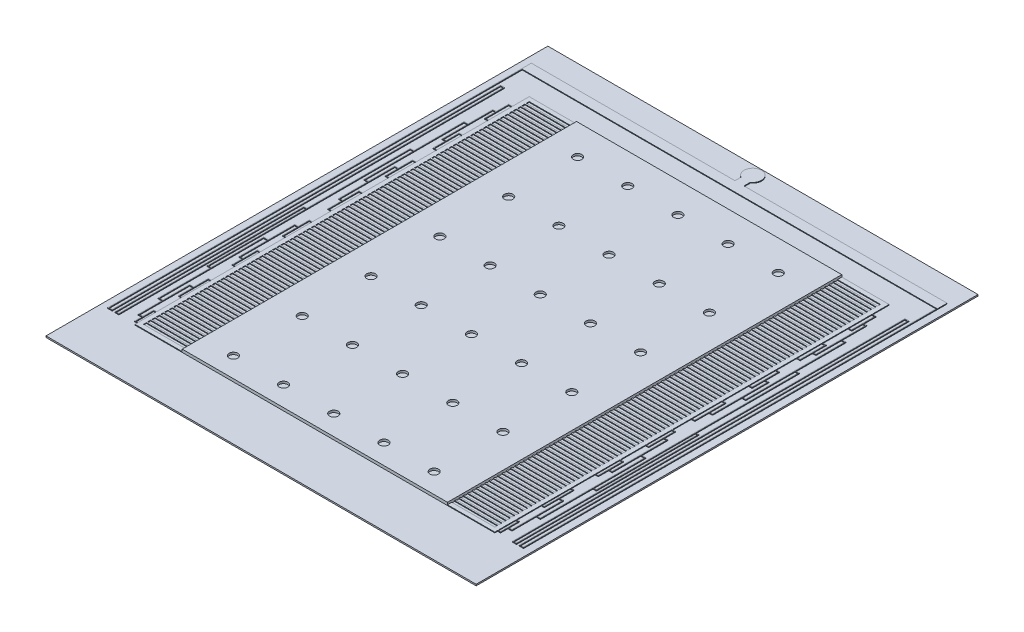
SolidWorks part; units mm, degrees
ref_plane "Front Plane" through (0, 0, 0) normal (0, 0, 1) x (1, 0, 0)
ref_plane "Top Plane" through (0, 0, 0) normal (0, 1, 0) x (1, 0, 0)
ref_plane "Right Plane" through (0, 0, 0) normal (1, 0, 0) x (0, 0, -1)
sketch "Sketch3" plane through (0, 0, 0) normal (0, 1, 0) x (1, 0, 0)
  line L1 (-15, 17.5) -> (15, 17.5)
  line L2 (-15, 17.5) -> (-15, -17.5)
  line L3 (-15, -17.5) -> (15, -17.5)
  line L4 (15, 17.5) -> (15, -17.5)
  line L5 (-15, 17.5) -> (15, -17.5) construction
  line L6 (-15, -17.5) -> (15, 17.5) construction
  point P0 (0, 0)
  dimension "D1" = 30
  dimension "D2" = 35
extrude "Boss-Extrude2" add sketch "Sketch3" along normal blind 0.1
sketch "Sketch4" plane through (0, 0.1, 0) normal (0, 1, 0) x (1, 0, 0)
  line L1 (-9.25, 13.75) -> (9.25, 13.75)
  line L2 (-9.25, 13.75) -> (-9.25, -13.75)
  line L3 (-9.25, -13.75) -> (9.25, -13.75)
  line L4 (9.25, 13.75) -> (9.25, -13.75)
  line L5 (-9.25, 13.75) -> (9.25, -13.75) construction
  line L6 (-9.25, -13.75) -> (9.25, 13.75) construction
  point P0 (0, 0)
  dimension "D1" = 18.5
  dimension "D2" = 27.5
sketch "Sketch6" plane through (0, 0.1, 0) normal (0, 1, 0) x (1, 0, 0)
  line L0 (-14.5, 15.8474) -> (14.5, 15.8474)
  line L1 (14.5, 15.8474) -> (14.5, -13.6942)
  line L2 (-14.5, 15.8474) -> (-14.5, -13.6942)
  line L3 (-9.25, 13.75) -> (-9.25, -13.75)
  line L4 (-9.25, 13.75) -> (-12.55, 13.75)
  line L5 (-9.25, -13.75) -> (-12.55, -13.75)
  line L6 (-12.55, 13.75) -> (-12.55, -13.75)
  line L7 (9.25, 13.75) -> (9.25, -13.75)
  line L8 (9.25, 13.75) -> (12.55, 13.75)
  line L9 (9.25, -13.75) -> (12.55, -13.75)
  line L10 (12.55, 13.75) -> (12.55, -13.75)
  line L11 (-12.55, 12.5818) -> (-12.8114, 12.5818)
  line L12 (-12.55, 12.5318) -> (-12.7614, 12.5318)
  line L13 (-12.55, 10.928) -> (-12.7614, 10.928)
  line L14 (-12.55, 10.878) -> (-12.8114, 10.878)
  line L15 (-12.7614, 12.5318) -> (-12.7614, 10.928)
  line L16 (-12.8114, 12.5818) -> (-12.8114, 11.7021)
  line L17 (-12.8114, 11.7021) -> (-13.0395, 11.7021)
  line L18 (-12.8114, 10.878) -> (-12.8114, 11.6521)
  line L19 (-12.8114, 11.6521) -> (-12.9895, 11.6521)
  line L20 (-12.55, 9.1125) -> (-12.8052, 9.1125)
  line L21 (-12.55, 9.0625) -> (-12.7552, 9.0625)
  line L22 (-12.7552, 9.0625) -> (-12.7552, 7.3412)
  line L23 (-12.7552, 7.3412) -> (-12.55, 7.3412)
  line L24 (-12.55, 7.2912) -> (-12.8052, 7.2912)
  line L25 (-12.8052, 7.2912) -> (-12.8052, 8.1575)
  line L26 (-13.0395, 11.7021) -> (-13.0395, 9.9736)
  line L27 (-12.8052, 9.1125) -> (-12.8052, 8.2075)
  line L28 (-12.8052, 8.2075) -> (-12.9895, 8.2075)
  line L29 (-12.55, 5.8632) -> (-12.7979, 5.8632)
  line L30 (-12.7979, 5.8632) -> (-12.7979, 4.8722)
  line L31 (-12.7979, 4.8722) -> (-13.0441, 4.8722)
  line L32 (-12.55, 3.9456) -> (-12.7979, 3.9456)
  line L33 (-12.7979, 3.9456) -> (-12.7979, 4.8222)
  line L34 (-12.7979, 4.8222) -> (-12.9941, 4.8222)
  line L35 (-12.55, 5.8132) -> (-12.7479, 5.8132)
  line L36 (-12.7479, 5.8132) -> (-12.7479, 3.9956)
  line L37 (-12.7479, 3.9956) -> (-12.55, 3.9956)
  line L38 (-12.55, 2.1314) -> (-12.8017, 2.1314)
  line L39 (-12.8017, 2.1314) -> (-12.8017, 0.9895)
  line L40 (-12.8017, 0.9895) -> (-12.9941, 0.9895)
  line L41 (-12.55, -0.05) -> (-12.8017, -0.05)
  line L42 (-12.8017, -0.05) -> (-12.8017, 0.9395)
  line L43 (-13.0441, 4.8722) -> (-13.0441, 3.0344)
  line L44 (-12.55, 2.0814) -> (-12.7517, 2.0814)
  line L45 (-12.7517, 2.0814) -> (-12.7517, 0)
  line L46 (-12.7517, 0) -> (-12.55, 0)
  line L47 (-12.55, -1.363) -> (-12.7705, -1.363)
  line L48 (-12.7705, -1.363) -> (-12.7705, -2.1377)
  line L49 (-13.0441, 3.0344) -> (-13.2661, 3.0344)
  line L50 (-12.55, -3.2374) -> (-12.7705, -3.2374)
  line L51 (-12.7705, -3.2374) -> (-12.7705, -2.1877)
  line L52 (-12.7705, -2.1877) -> (-12.9647, -2.1877)
  line L53 (-12.55, -1.413) -> (-12.7205, -1.413)
  line L54 (-12.7205, -1.413) -> (-12.7205, -3.1874)
  line L55 (-12.7205, -3.1874) -> (-12.55, -3.1874)
  line L56 (-12.55, -4.9884) -> (-12.7705, -4.9884)
  line L57 (-12.7705, -4.9884) -> (-12.7705, -5.9807)
  line L58 (-12.7705, -5.9807) -> (-12.9647, -5.9807)
  line L59 (-12.55, -6.7484) -> (-12.7705, -6.7484)
  line L60 (-12.7705, -6.7484) -> (-12.7705, -6.0307)
  line L61 (-12.8017, 0.9395) -> (-13.0441, 0.9395)
  line L62 (-12.7205, -5.0384) -> (-12.7205, -6.6984)
  line L63 (-12.7205, -6.6984) -> (-12.55, -6.6984)
  line L64 (-12.7205, -5.0384) -> (-12.55, -5.0384)
  line L65 (-12.55, -8.422) -> (-12.7572, -8.422)
  line L66 (-12.7572, -8.422) -> (-12.7572, -9.4377)
  line L67 (-13.0441, 0.9395) -> (-13.0441, 2.9844)
  line L68 (-12.55, -10.502) -> (-12.7572, -10.502)
  line L69 (-12.7572, -10.502) -> (-12.7572, -9.4877)
  line L70 (-12.7572, -9.4877) -> (-12.9899, -9.4877)
  line L71 (-12.55, -8.472) -> (-12.7072, -8.472)
  line L72 (-12.7072, -8.472) -> (-12.7072, -10.452)
  line L73 (-12.7072, -10.452) -> (-12.55, -10.452)
  line L74 (-12.55, -12.2327) -> (-12.7572, -12.2327)
  line L75 (-12.7572, -12.2327) -> (-12.7572, -12.9898)
  line L76 (-12.7572, -12.9898) -> (-12.9899, -12.9898)
  line L77 (-12.55, -13.5571) -> (-12.7572, -13.5571)
  line L78 (-12.7572, -13.5571) -> (-12.7572, -13.0398)
  line L79 (-13.0395, 9.9736) -> (-13.3161, 9.9736)
  line L80 (-12.7072, -12.2827) -> (-12.7072, -13.5071)
  line L81 (-12.7072, -13.5071) -> (-12.55, -13.5071)
  line L82 (-13.3161, 9.9736) -> (-13.3161, 6.4717)
  line L83 (-12.8052, 8.1575) -> (-13.0395, 8.1575)
  line L84 (-13.0395, 8.1575) -> (-13.0395, 9.9236)
  line L85 (-13.0395, 9.9236) -> (-13.2661, 9.9236)
  line L86 (-12.9895, 11.6521) -> (-12.9895, 8.2075)
  line L87 (-12.9941, 4.8222) -> (-12.9941, 0.9895)
  line L88 (-12.7705, -6.0307) -> (-13.0147, -6.0307)
  line L89 (-13.0147, -6.0307) -> (-13.0147, -4.0382)
  line L90 (-13.0147, -4.0382) -> (-13.2808, -4.0382)
  line L91 (-12.7705, -2.1377) -> (-13.0147, -2.1377)
  line L92 (-13.0147, -2.1377) -> (-13.0147, -3.9882)
  line L93 (-13.0147, -3.9882) -> (-13.3308, -3.9882)
  line L94 (-12.9647, -2.1877) -> (-12.9647, -5.9807)
  line L95 (-12.7572, -9.4377) -> (-13.0399, -9.4377)
  line L96 (-13.0399, -9.4377) -> (-13.0399, -11.3027)
  line L97 (-13.0399, -11.3027) -> (-13.2808, -11.3027)
  line L98 (-12.7572, -13.0398) -> (-13.0399, -13.0398)
  line L99 (-13.0399, -13.0398) -> (-13.0399, -11.3527)
  line L100 (-13.3308, -3.9882) -> (-13.3308, -7.6362)
  line L101 (-12.9899, -9.4877) -> (-12.9899, -12.9898)
  line L102 (-13.3161, 6.4717) -> (-13.5698, 6.4717)
  line L103 (-13.3161, 2.9844) -> (-13.3161, 6.4217)
  line L104 (-13.3161, 6.4217) -> (-13.5198, 6.4217)
  line L105 (-13.2661, 9.9236) -> (-13.2661, 3.0344)
  line L106 (-13.3161, 2.9844) -> (-13.0441, 2.9844)
  line L107 (-13.3308, -7.6362) -> (-13.5198, -7.6362)
  line L108 (-13.0399, -11.3527) -> (-13.3308, -11.3527)
  line L109 (-13.3308, -11.3527) -> (-13.3308, -7.6862)
  line L110 (-13.5698, 6.4717) -> (-13.5698, -0.7493)
  line L111 (-13.2808, -4.0382) -> (-13.2808, -11.3027)
  line L112 (-13.5698, -0.7493) -> (-13.7743, -0.7493)
  line L113 (-13.3308, -7.6862) -> (-13.5698, -7.6862)
  line L114 (-13.5698, -7.6862) -> (-13.5698, -0.7993)
  line L115 (-13.5198, -7.6362) -> (-13.5198, 6.4217)
  line L116 (-12.7072, -12.2827) -> (-12.55, -12.2827)
  line L117 (-14.5, -13.6942) -> (-14.189, -13.6942)
  line L118 (-14.45, 15.1627) -> (14.45, 15.1627)
  line L119 (-14.45, 15.1627) -> (-14.45, -13.6442)
  line L120 (-14.45, -13.6442) -> (-14.239, -13.6442)
  line L121 (-14.239, -13.6442) -> (-14.239, 13.4436)
  line L122 (-14.239, 13.4436) -> (-13.9579, 13.4436)
  line L123 (-13.9579, 13.4436) -> (-13.9579, -13.646)
  line L124 (-13.9579, -13.646) -> (-13.7743, -13.646)
  line L125 (-13.7743, -13.646) -> (-13.7743, -0.7493)
  line L126 (-14.189, -13.6942) -> (-14.189, 13.3936)
  line L127 (-14.189, 13.3936) -> (-14.0079, 13.3936)
  line L128 (-14.0079, 13.3936) -> (-14.0079, -13.696)
  line L129 (-14.0079, -13.696) -> (-13.7243, -13.696)
  line L130 (-13.7243, -13.696) -> (-13.7243, -0.7993)
  line L131 (-13.7243, -0.7993) -> (-13.5698, -0.7993)
  line L132 (0, -18.8163) -> (0, 18.8163) construction
  line L134 (14.45, 15.1627) -> (14.45, -13.6442)
  line L135 (14.0079, -13.696) -> (13.7243, -13.696)
  line L136 (13.9579, -13.646) -> (13.7743, -13.646)
  line L137 (14.5, -13.6942) -> (14.189, -13.6942)
  line L138 (14.45, -13.6442) -> (14.239, -13.6442)
  line L139 (12.7572, -13.5571) -> (12.7572, -13.0398)
  line L140 (12.55, -13.5571) -> (12.7572, -13.5571)
  line L141 (12.7072, -13.5071) -> (12.55, -13.5071)
  line L142 (12.7572, -13.0398) -> (13.0399, -13.0398)
  line L143 (12.7572, -12.9898) -> (12.9899, -12.9898)
  line L144 (12.7072, -12.2827) -> (12.55, -12.2827)
  line L145 (12.7572, -12.2327) -> (12.7572, -12.9898)
  line L146 (12.7072, -12.2827) -> (12.7072, -13.5071)
  line L147 (12.55, -12.2327) -> (12.7572, -12.2327)
  line L148 (13.0399, -13.0398) -> (13.0399, -11.3527)
  line L149 (13.0399, -11.3527) -> (13.3308, -11.3527)
  line L150 (13.0399, -11.3027) -> (13.2808, -11.3027)
  line L151 (12.55, -10.502) -> (12.7572, -10.502)
  line L152 (12.7072, -10.452) -> (12.55, -10.452)
  line L153 (12.7572, -10.502) -> (12.7572, -9.4877)
  line L154 (13.0399, -9.4377) -> (13.0399, -11.3027)
  line L155 (12.9899, -9.4877) -> (12.9899, -12.9898)
  line L156 (12.7572, -9.4877) -> (12.9899, -9.4877)
  line L157 (12.7572, -9.4377) -> (13.0399, -9.4377)
  line L158 (12.7572, -8.422) -> (12.7572, -9.4377)
  line L159 (12.7072, -8.472) -> (12.7072, -10.452)
  line L160 (12.55, -8.472) -> (12.7072, -8.472)
  line L161 (12.55, -8.422) -> (12.7572, -8.422)
  line L162 (13.3308, -11.3527) -> (13.3308, -7.6862)
  line L163 (13.3308, -7.6862) -> (13.5698, -7.6862)
  line L164 (13.3308, -7.6362) -> (13.5198, -7.6362)
  line L165 (12.55, -6.7484) -> (12.7705, -6.7484)
  line L166 (12.7205, -6.6984) -> (12.55, -6.6984)
  line L167 (12.7705, -6.7484) -> (12.7705, -6.0307)
  line L168 (12.7705, -6.0307) -> (13.0147, -6.0307)
  line L169 (12.7705, -5.9807) -> (12.9647, -5.9807)
  line L170 (12.7705, -4.9884) -> (12.7705, -5.9807)
  line L171 (12.7205, -5.0384) -> (12.7205, -6.6984)
  line L172 (12.7205, -5.0384) -> (12.55, -5.0384)
  line L173 (12.55, -4.9884) -> (12.7705, -4.9884)
  line L174 (13.0147, -6.0307) -> (13.0147, -4.0382)
  line L175 (13.3308, -3.9882) -> (13.3308, -7.6362)
  line L176 (13.2808, -4.0382) -> (13.2808, -11.3027)
  line L177 (13.0147, -4.0382) -> (13.2808, -4.0382)
  line L178 (13.0147, -3.9882) -> (13.3308, -3.9882)
  line L179 (12.55, -3.2374) -> (12.7705, -3.2374)
  line L180 (12.7205, -3.1874) -> (12.55, -3.1874)
  line L181 (13.0147, -2.1377) -> (13.0147, -3.9882)
  line L182 (12.9647, -2.1877) -> (12.9647, -5.9807)
  line L183 (12.7705, -3.2374) -> (12.7705, -2.1877)
  line L184 (12.7705, -2.1877) -> (12.9647, -2.1877)
  line L185 (12.7705, -2.1377) -> (13.0147, -2.1377)
  line L186 (12.7205, -1.413) -> (12.7205, -3.1874)
  line L187 (12.7705, -1.363) -> (12.7705, -2.1377)
  line L188 (12.55, -1.413) -> (12.7205, -1.413)
  line L189 (12.55, -1.363) -> (12.7705, -1.363)
  line L190 (13.5698, -7.6862) -> (13.5698, -0.7993)
  line L191 (13.7243, -13.696) -> (13.7243, -0.7993)
  line L192 (13.7743, -13.646) -> (13.7743, -0.7493)
  line L193 (13.7243, -0.7993) -> (13.5698, -0.7993)
  line L194 (13.5698, -0.7493) -> (13.7743, -0.7493)
  line L195 (12.55, -0.05) -> (12.8017, -0.05)
  line L196 (12.7517, 0) -> (12.55, 0)
  line L197 (12.8017, -0.05) -> (12.8017, 0.9395)
  line L198 (12.8017, 0.9395) -> (13.0441, 0.9395)
  line L199 (12.8017, 0.9895) -> (12.9941, 0.9895)
  line L200 (12.7517, 2.0814) -> (12.7517, 0)
  line L201 (12.8017, 2.1314) -> (12.8017, 0.9895)
  line L202 (12.55, 2.0814) -> (12.7517, 2.0814)
  line L203 (12.55, 2.1314) -> (12.8017, 2.1314)
  line L204 (13.0441, 3.0344) -> (13.2661, 3.0344)
  line L205 (13.3161, 2.9844) -> (13.0441, 2.9844)
  line L206 (13.0441, 0.9395) -> (13.0441, 2.9844)
  line L207 (12.55, 3.9456) -> (12.7979, 3.9456)
  line L208 (12.7479, 3.9956) -> (12.55, 3.9956)
  line L209 (13.0441, 4.8722) -> (13.0441, 3.0344)
  line L210 (12.9941, 4.8222) -> (12.9941, 0.9895)
  line L211 (12.7979, 3.9456) -> (12.7979, 4.8222)
  line L212 (12.7979, 4.8222) -> (12.9941, 4.8222)
  line L213 (12.7979, 4.8722) -> (13.0441, 4.8722)
  line L214 (12.7479, 5.8132) -> (12.7479, 3.9956)
  line L215 (12.7979, 5.8632) -> (12.7979, 4.8722)
  line L216 (12.55, 5.8132) -> (12.7479, 5.8132)
  line L217 (12.55, 5.8632) -> (12.7979, 5.8632)
  line L218 (13.3161, 2.9844) -> (13.3161, 6.4217)
  line L219 (13.5698, 6.4717) -> (13.5698, -0.7493)
  line L220 (13.5198, -7.6362) -> (13.5198, 6.4217)
  line L221 (13.3161, 6.4217) -> (13.5198, 6.4217)
  line L222 (13.3161, 6.4717) -> (13.5698, 6.4717)
  line L223 (12.55, 7.2912) -> (12.8052, 7.2912)
  line L224 (12.7552, 7.3412) -> (12.55, 7.3412)
  line L225 (12.8052, 7.2912) -> (12.8052, 8.1575)
  line L226 (12.8052, 8.1575) -> (13.0395, 8.1575)
  line L227 (12.8052, 8.2075) -> (12.9895, 8.2075)
  line L228 (12.7552, 9.0625) -> (12.7552, 7.3412)
  line L229 (12.8052, 9.1125) -> (12.8052, 8.2075)
  line L230 (12.55, 9.0625) -> (12.7552, 9.0625)
  line L231 (12.55, 9.1125) -> (12.8052, 9.1125)
  line L232 (13.0395, 8.1575) -> (13.0395, 9.9236)
  line L233 (13.3161, 9.9736) -> (13.3161, 6.4717)
  line L234 (13.2661, 9.9236) -> (13.2661, 3.0344)
  line L235 (13.0395, 9.9236) -> (13.2661, 9.9236)
  line L236 (13.0395, 9.9736) -> (13.3161, 9.9736)
  line L237 (12.55, 10.878) -> (12.8114, 10.878)
  line L238 (12.55, 10.928) -> (12.7614, 10.928)
  line L239 (13.0395, 11.7021) -> (13.0395, 9.9736)
  line L240 (12.9895, 11.6521) -> (12.9895, 8.2075)
  line L241 (12.8114, 10.878) -> (12.8114, 11.6521)
  line L242 (12.8114, 11.6521) -> (12.9895, 11.6521)
  line L243 (12.8114, 11.7021) -> (13.0395, 11.7021)
  line L244 (13.9579, 13.4436) -> (13.9579, -13.646)
  line L245 (14.0079, 13.3936) -> (14.0079, -13.696)
  line L246 (14.189, -13.6942) -> (14.189, 13.3936)
  line L247 (14.239, -13.6442) -> (14.239, 13.4436)
  line L248 (14.189, 13.3936) -> (14.0079, 13.3936)
  line L249 (14.239, 13.4436) -> (13.9579, 13.4436)
  line L250 (12.7614, 12.5318) -> (12.7614, 10.928)
  line L251 (12.8114, 12.5818) -> (12.8114, 11.7021)
  line L252 (12.55, 12.5318) -> (12.7614, 12.5318)
  line L253 (12.55, 12.5818) -> (12.8114, 12.5818)
  line L254 (-0.2968, 16.2659) -> (-0.2968, 15.8474)
  line L255 (0.336, 16.2899) -> (0.336, 15.8474)
  circle A0 centre (0, 16.7949) radius 0.6065
  point P0 (-12.55, 0)
  point P3 (0, 15.8474)
  point P14 (-12.55, 0)
  point P19 (-12.55, 7.2912)
  point P21 (-12.55, 10.928)
  point P22 (-12.55, 12.4686)
  point P23 (-12.55, 9.0625)
  point P24 (-12.55, 3.9833)
  point P25 (-12.55, 5.8132)
  point P26 (-12.55, 2.0814)
  point P27 (-12.55, -6.7484)
  point P28 (-12.55, -3.2374)
  point P29 (-12.55, -1.413)
  point P30 (-12.55, -5.0384)
  point P31 (-12.55, -10.502)
  point P32 (-12.55, -8.472)
  point P33 (-12.55, -12.1448)
  point P157 (-13.647, -0.7993)
  point P158 (-12.6352, -6.6984)
  point P162 (0, 15.1627)
  point P177 (0, 0)
  dimension "D1" = 3.3
  dimension "D2" = 3.3
  dimension "D3" = 29
  dimension "D4" = 0.05
  dimension "D5" = 0.05
  dimension "D6" = 0.05
  dimension "D7" = 0.05
  dimension "D8" = 0.05
  dimension "D9" = 0.05
  dimension "D10" = 0.05
  dimension "D11" = 0.05
  dimension "D12" = 0.05
  dimension "D13" = 0.05
  dimension "D14" = 0.05
  dimension "D15" = 0.05
  dimension "D16" = 0.05
  dimension "D17" = 0.05
  dimension "D18" = 0.05
  dimension "D19" = 0.05
  dimension "D20" = 0.05
  dimension "D21" = 0.05
  dimension "D22" = 0.05
  dimension "D23" = 0.05
  dimension "D24" = 0.05
  dimension "D25" = 0.05
  dimension "D26" = 0.05
  dimension "D27" = 0.05
  dimension "D28" = 0.05
  dimension "D29" = 0.05
  dimension "D30" = 0.05
  dimension "D31" = 0.05
  dimension "D32" = 0.05
  dimension "D33" = 0.05
  dimension "D34" = 0.05
  dimension "D35" = 0.05
  dimension "D36" = 0.05
  dimension "D37" = 0.05
  dimension "D38" = 0.05
  dimension "D39" = 0.05
  dimension "D40" = 0.05
  dimension "D41" = 0.05
  dimension "D42" = 0.05
  dimension "D43" = 0.05
  dimension "D44" = 0.05
  dimension "D45" = 0.05
  dimension "D46" = 0.05
  dimension "D47" = 0.05
  dimension "D48" = 0.05
  dimension "D49" = 0.05
  dimension "D50" = 0.05
  dimension "D51" = 0.05
  dimension "D52" = 0.05
  dimension "D53" = 0.05
  dimension "D54" = 0.05
  dimension "D55" = 0.05
  dimension "D56" = 0.05
extrude "Boss-Extrude5" add sketch "Sketch4" along normal blind 0.2 separate body
extrude "Boss-Extrude10" add sketch "Sketch6" along normal blind 0.05 contours L132 L118 L134 L138 L247 L249 L244 L136 L192 L194 L219 L222 L233 L236 L239 L243 L251 L253 L10 L252 L250 L238 L237 L241 L242 L240 L227 L229 L231 L230 L228 L224 L223 L225 L226 L232 L235 L234 L204 L209 L213 L215 L217 L216 L214 L208 | L0 L132 A0 L254 | L132 L0 L255 A0 | A0 L132 | L132 A0 | L118 L132 L0 L2 L117 L126 L127 L128 L129 L130 L131 L114 L113 L109 L108 L99 L98 L78 L77 L6 L81 L80 L116 L74 L75 L76 L101 L70 L69 L68 L73 L72 L71 L65 L66 L95 L96 L97 L111 L90 L89 L88 L60 L59 L63 L62 | L10 L8 L7 L9 | L4 L6 L5 L3 | L3 L4 L6 L5 | L7 L8 L10 L9 region at (-7.3984, 0.1, -15.5183) region at (-0.1536, 0.1, -16.0312) region at (0.1754, 0.1, -16.0354) region at (0.168, 0.1, -15.5183) region at (-0.2574, 0.1, -16.7949) region at (0.2574, 0.1, -16.7949) region at (-10.9, 0.1, 0) region at (10.9, 0.1, 0)
sketch "Sketch7" plane through (0, 0.1, 0) normal (0, 1, 0) x (1, 0, 0)
  line L0 (9.25, 13.45) -> (12.25, 13.45)
  line L1 (9.25, 13.45) -> (9.25, 13.25)
  line L2 (12.25, 13.45) -> (12.25, 13.25)
  line L3 (9.25, 13.25) -> (12.25, 13.25)
  line L4 (9.25, -13.75) -> (9.25, 13.75) construction
  line L7 (9.25, 13.15) -> (12.25, 13.15)
  line L8 (9.25, 13.15) -> (9.25, 12.95)
  line L9 (9.25, 12.95) -> (12.25, 12.95)
  line L10 (12.25, 13.15) -> (12.25, 12.95)
  line L11 (9.25, 12.85) -> (12.25, 12.85)
  line L12 (9.25, 12.85) -> (9.25, 12.65)
  line L13 (9.25, 12.65) -> (12.25, 12.65)
  line L14 (12.25, 12.85) -> (12.25, 12.65)
  line L15 (9.25, 12.55) -> (12.25, 12.55)
  line L16 (9.25, 12.55) -> (9.25, 12.35)
  line L17 (9.25, 12.35) -> (12.25, 12.35)
  line L18 (12.25, 12.55) -> (12.25, 12.35)
  line L19 (9.25, 12.25) -> (12.25, 12.25)
  line L20 (9.25, 12.25) -> (9.25, 12.05)
  line L21 (9.25, 12.05) -> (12.25, 12.05)
  line L22 (12.25, 12.25) -> (12.25, 12.05)
  line L23 (9.25, 11.95) -> (12.25, 11.95)
  line L24 (9.25, 11.95) -> (9.25, 11.75)
  line L25 (9.25, 11.75) -> (12.25, 11.75)
  line L26 (12.25, 11.95) -> (12.25, 11.75)
  line L27 (9.25, 11.65) -> (12.25, 11.65)
  line L28 (9.25, 11.65) -> (9.25, 11.45)
  line L29 (9.25, 11.45) -> (12.25, 11.45)
  line L30 (12.25, 11.65) -> (12.25, 11.45)
  line L31 (9.25, 11.35) -> (12.25, 11.35)
  line L32 (9.25, 11.35) -> (9.25, 11.15)
  line L33 (9.25, 11.15) -> (12.25, 11.15)
  line L34 (12.25, 11.35) -> (12.25, 11.15)
  line L35 (9.25, 11.05) -> (12.25, 11.05)
  line L36 (9.25, 11.05) -> (9.25, 10.85)
  line L37 (9.25, 10.85) -> (12.25, 10.85)
  line L38 (12.25, 11.05) -> (12.25, 10.85)
  line L39 (9.25, 10.75) -> (12.25, 10.75)
  line L40 (9.25, 10.75) -> (9.25, 10.55)
  line L41 (9.25, 10.55) -> (12.25, 10.55)
  line L42 (12.25, 10.75) -> (12.25, 10.55)
  line L43 (9.25, 10.45) -> (12.25, 10.45)
  line L44 (9.25, 10.45) -> (9.25, 10.25)
  line L45 (9.25, 10.25) -> (12.25, 10.25)
  line L46 (12.25, 10.45) -> (12.25, 10.25)
  line L47 (9.25, 10.15) -> (12.25, 10.15)
  line L48 (9.25, 10.15) -> (9.25, 9.95)
  line L49 (9.25, 9.95) -> (12.25, 9.95)
  line L50 (12.25, 10.15) -> (12.25, 9.95)
  line L51 (9.25, 9.85) -> (12.25, 9.85)
  line L52 (9.25, 9.85) -> (9.25, 9.65)
  line L53 (9.25, 9.65) -> (12.25, 9.65)
  line L54 (12.25, 9.85) -> (12.25, 9.65)
  line L55 (9.25, 9.55) -> (12.25, 9.55)
  line L56 (9.25, 9.55) -> (9.25, 9.35)
  line L57 (9.25, 9.35) -> (12.25, 9.35)
  line L58 (12.25, 9.55) -> (12.25, 9.35)
  line L59 (9.25, 9.25) -> (12.25, 9.25)
  line L60 (9.25, 9.25) -> (9.25, 9.05)
  line L61 (9.25, 9.05) -> (12.25, 9.05)
  line L62 (12.25, 9.25) -> (12.25, 9.05)
  line L63 (9.25, 8.95) -> (12.25, 8.95)
  line L64 (9.25, 8.95) -> (9.25, 8.75)
  line L65 (9.25, 8.75) -> (12.25, 8.75)
  line L66 (12.25, 8.95) -> (12.25, 8.75)
  line L67 (9.25, 8.65) -> (12.25, 8.65)
  line L68 (9.25, 8.65) -> (9.25, 8.45)
  line L69 (9.25, 8.45) -> (12.25, 8.45)
  line L70 (12.25, 8.65) -> (12.25, 8.45)
  line L71 (9.25, 8.35) -> (12.25, 8.35)
  line L72 (9.25, 8.35) -> (9.25, 8.15)
  line L73 (9.25, 8.15) -> (12.25, 8.15)
  line L74 (12.25, 8.35) -> (12.25, 8.15)
  line L75 (9.25, 8.05) -> (12.25, 8.05)
  line L76 (9.25, 8.05) -> (9.25, 7.85)
  line L77 (9.25, 7.85) -> (12.25, 7.85)
  line L78 (12.25, 8.05) -> (12.25, 7.85)
  line L79 (9.25, 7.75) -> (12.25, 7.75)
  line L80 (9.25, 7.75) -> (9.25, 7.55)
  line L81 (9.25, 7.55) -> (12.25, 7.55)
  line L82 (12.25, 7.75) -> (12.25, 7.55)
  line L83 (9.25, 7.45) -> (12.25, 7.45)
  line L84 (9.25, 7.45) -> (9.25, 7.25)
  line L85 (9.25, 7.25) -> (12.25, 7.25)
  line L86 (12.25, 7.45) -> (12.25, 7.25)
  line L87 (9.25, 7.15) -> (12.25, 7.15)
  line L88 (9.25, 7.15) -> (9.25, 6.95)
  line L89 (9.25, 6.95) -> (12.25, 6.95)
  line L90 (12.25, 7.15) -> (12.25, 6.95)
  line L91 (9.25, 6.85) -> (12.25, 6.85)
  line L92 (9.25, 6.85) -> (9.25, 6.65)
  line L93 (9.25, 6.65) -> (12.25, 6.65)
  line L94 (12.25, 6.85) -> (12.25, 6.65)
  line L95 (9.25, 6.55) -> (12.25, 6.55)
  line L96 (9.25, 6.55) -> (9.25, 6.35)
  line L97 (9.25, 6.35) -> (12.25, 6.35)
  line L98 (12.25, 6.55) -> (12.25, 6.35)
  line L99 (9.25, 6.25) -> (12.25, 6.25)
  line L100 (9.25, 6.25) -> (9.25, 6.05)
  line L101 (9.25, 6.05) -> (12.25, 6.05)
  line L102 (12.25, 6.25) -> (12.25, 6.05)
  line L103 (9.25, 5.95) -> (12.25, 5.95)
  line L104 (9.25, 5.95) -> (9.25, 5.75)
  line L105 (9.25, 5.75) -> (12.25, 5.75)
  line L106 (12.25, 5.95) -> (12.25, 5.75)
  line L107 (9.25, 5.65) -> (12.25, 5.65)
  line L108 (9.25, 5.65) -> (9.25, 5.45)
  line L109 (9.25, 5.45) -> (12.25, 5.45)
  line L110 (12.25, 5.65) -> (12.25, 5.45)
  line L111 (9.25, 5.35) -> (12.25, 5.35)
  line L112 (9.25, 5.35) -> (9.25, 5.15)
  line L113 (9.25, 5.15) -> (12.25, 5.15)
  line L114 (12.25, 5.35) -> (12.25, 5.15)
  line L115 (9.25, 5.05) -> (12.25, 5.05)
  line L116 (9.25, 5.05) -> (9.25, 4.85)
  line L117 (9.25, 4.85) -> (12.25, 4.85)
  line L118 (12.25, 5.05) -> (12.25, 4.85)
  line L119 (9.25, 4.75) -> (12.25, 4.75)
  line L120 (9.25, 4.75) -> (9.25, 4.55)
  line L121 (9.25, 4.55) -> (12.25, 4.55)
  line L122 (12.25, 4.75) -> (12.25, 4.55)
  line L123 (9.25, 4.45) -> (12.25, 4.45)
  line L124 (9.25, 4.45) -> (9.25, 4.25)
  line L125 (9.25, 4.25) -> (12.25, 4.25)
  line L126 (12.25, 4.45) -> (12.25, 4.25)
  line L127 (9.25, 4.15) -> (12.25, 4.15)
  line L128 (9.25, 4.15) -> (9.25, 3.95)
  line L129 (9.25, 3.95) -> (12.25, 3.95)
  line L130 (12.25, 4.15) -> (12.25, 3.95)
  line L131 (9.25, 3.85) -> (12.25, 3.85)
  line L132 (9.25, 3.85) -> (9.25, 3.65)
  line L133 (9.25, 3.65) -> (12.25, 3.65)
  line L134 (12.25, 3.85) -> (12.25, 3.65)
  line L135 (9.25, 3.55) -> (12.25, 3.55)
  line L136 (9.25, 3.55) -> (9.25, 3.35)
  line L137 (9.25, 3.35) -> (12.25, 3.35)
  line L138 (12.25, 3.55) -> (12.25, 3.35)
  line L139 (9.25, 3.25) -> (12.25, 3.25)
  line L140 (9.25, 3.25) -> (9.25, 3.05)
  line L141 (9.25, 3.05) -> (12.25, 3.05)
  line L142 (12.25, 3.25) -> (12.25, 3.05)
  line L143 (9.25, 2.95) -> (12.25, 2.95)
  line L144 (9.25, 2.95) -> (9.25, 2.75)
  line L145 (9.25, 2.75) -> (12.25, 2.75)
  line L146 (12.25, 2.95) -> (12.25, 2.75)
  line L147 (9.25, 2.65) -> (12.25, 2.65)
  line L148 (9.25, 2.65) -> (9.25, 2.45)
  line L149 (9.25, 2.45) -> (12.25, 2.45)
  line L150 (12.25, 2.65) -> (12.25, 2.45)
  line L151 (9.25, 2.35) -> (12.25, 2.35)
  line L152 (9.25, 2.35) -> (9.25, 2.15)
  line L153 (9.25, 2.15) -> (12.25, 2.15)
  line L154 (12.25, 2.35) -> (12.25, 2.15)
  line L155 (9.25, 2.05) -> (12.25, 2.05)
  line L156 (9.25, 2.05) -> (9.25, 1.85)
  line L157 (9.25, 1.85) -> (12.25, 1.85)
  line L158 (12.25, 2.05) -> (12.25, 1.85)
  line L159 (9.25, 1.75) -> (12.25, 1.75)
  line L160 (9.25, 1.75) -> (9.25, 1.55)
  line L161 (9.25, 1.55) -> (12.25, 1.55)
  line L162 (12.25, 1.75) -> (12.25, 1.55)
  line L163 (9.25, 1.45) -> (12.25, 1.45)
  line L164 (9.25, 1.45) -> (9.25, 1.25)
  line L165 (9.25, 1.25) -> (12.25, 1.25)
  line L166 (12.25, 1.45) -> (12.25, 1.25)
  line L167 (9.25, 1.15) -> (12.25, 1.15)
  line L168 (9.25, 1.15) -> (9.25, 0.95)
  line L169 (9.25, 0.95) -> (12.25, 0.95)
  line L170 (12.25, 1.15) -> (12.25, 0.95)
  line L171 (9.25, 0.85) -> (12.25, 0.85)
  line L172 (9.25, 0.85) -> (9.25, 0.65)
  line L173 (9.25, 0.65) -> (12.25, 0.65)
  line L174 (12.25, 0.85) -> (12.25, 0.65)
  line L175 (9.25, 0.55) -> (12.25, 0.55)
  line L176 (9.25, 0.55) -> (9.25, 0.35)
  line L177 (9.25, 0.35) -> (12.25, 0.35)
  line L178 (12.25, 0.55) -> (12.25, 0.35)
  line L179 (9.25, 0.25) -> (12.25, 0.25)
  line L180 (9.25, 0.25) -> (9.25, 0.05)
  line L181 (9.25, 0.05) -> (12.25, 0.05)
  line L182 (12.25, 0.25) -> (12.25, 0.05)
  line L183 (9.25, -0.05) -> (12.25, -0.05)
  line L184 (9.25, -0.05) -> (9.25, -0.25)
  line L185 (9.25, -0.25) -> (12.25, -0.25)
  line L186 (12.25, -0.05) -> (12.25, -0.25)
  line L187 (9.25, -0.35) -> (12.25, -0.35)
  line L188 (9.25, -0.35) -> (9.25, -0.55)
  line L189 (9.25, -0.55) -> (12.25, -0.55)
  line L190 (12.25, -0.35) -> (12.25, -0.55)
  line L191 (9.25, -0.65) -> (12.25, -0.65)
  line L192 (9.25, -0.65) -> (9.25, -0.85)
  line L193 (9.25, -0.85) -> (12.25, -0.85)
  line L194 (12.25, -0.65) -> (12.25, -0.85)
  line L195 (9.25, -0.95) -> (12.25, -0.95)
  line L196 (9.25, -0.95) -> (9.25, -1.15)
  line L197 (9.25, -1.15) -> (12.25, -1.15)
  line L198 (12.25, -0.95) -> (12.25, -1.15)
  line L199 (9.25, -1.25) -> (12.25, -1.25)
  line L200 (9.25, -1.25) -> (9.25, -1.45)
  line L201 (9.25, -1.45) -> (12.25, -1.45)
  line L202 (12.25, -1.25) -> (12.25, -1.45)
  line L203 (9.25, -1.55) -> (12.25, -1.55)
  line L204 (9.25, -1.55) -> (9.25, -1.75)
  line L205 (9.25, -1.75) -> (12.25, -1.75)
  line L206 (12.25, -1.55) -> (12.25, -1.75)
  line L207 (9.25, -1.85) -> (12.25, -1.85)
  line L208 (9.25, -1.85) -> (9.25, -2.05)
  line L209 (9.25, -2.05) -> (12.25, -2.05)
  line L210 (12.25, -1.85) -> (12.25, -2.05)
  line L211 (9.25, -2.15) -> (12.25, -2.15)
  line L212 (9.25, -2.15) -> (9.25, -2.35)
  line L213 (9.25, -2.35) -> (12.25, -2.35)
  line L214 (12.25, -2.15) -> (12.25, -2.35)
  line L215 (9.25, -2.45) -> (12.25, -2.45)
  line L216 (9.25, -2.45) -> (9.25, -2.65)
  line L217 (9.25, -2.65) -> (12.25, -2.65)
  line L218 (12.25, -2.45) -> (12.25, -2.65)
  line L219 (9.25, -2.75) -> (12.25, -2.75)
  line L220 (9.25, -2.75) -> (9.25, -2.95)
  line L221 (9.25, -2.95) -> (12.25, -2.95)
  line L222 (12.25, -2.75) -> (12.25, -2.95)
  line L223 (9.25, -3.05) -> (12.25, -3.05)
  line L224 (9.25, -3.05) -> (9.25, -3.25)
  line L225 (9.25, -3.25) -> (12.25, -3.25)
  line L226 (12.25, -3.05) -> (12.25, -3.25)
  line L227 (9.25, -3.35) -> (12.25, -3.35)
  line L228 (9.25, -3.35) -> (9.25, -3.55)
  line L229 (9.25, -3.55) -> (12.25, -3.55)
  line L230 (12.25, -3.35) -> (12.25, -3.55)
  line L231 (9.25, -3.65) -> (12.25, -3.65)
  line L232 (9.25, -3.65) -> (9.25, -3.85)
  line L233 (9.25, -3.85) -> (12.25, -3.85)
  line L234 (12.25, -3.65) -> (12.25, -3.85)
  line L235 (9.25, -3.95) -> (12.25, -3.95)
  line L236 (9.25, -3.95) -> (9.25, -4.15)
  line L237 (9.25, -4.15) -> (12.25, -4.15)
  line L238 (12.25, -3.95) -> (12.25, -4.15)
  line L239 (9.25, -4.25) -> (12.25, -4.25)
  line L240 (9.25, -4.25) -> (9.25, -4.45)
  line L241 (9.25, -4.45) -> (12.25, -4.45)
  line L242 (12.25, -4.25) -> (12.25, -4.45)
  line L243 (9.25, -4.55) -> (12.25, -4.55)
  line L244 (9.25, -4.55) -> (9.25, -4.75)
  line L245 (9.25, -4.75) -> (12.25, -4.75)
  line L246 (12.25, -4.55) -> (12.25, -4.75)
  line L247 (9.25, -4.85) -> (12.25, -4.85)
  line L248 (9.25, -4.85) -> (9.25, -5.05)
  line L249 (9.25, -5.05) -> (12.25, -5.05)
  line L250 (12.25, -4.85) -> (12.25, -5.05)
  line L251 (9.25, -5.15) -> (12.25, -5.15)
  line L252 (9.25, -5.15) -> (9.25, -5.35)
  line L253 (9.25, -5.35) -> (12.25, -5.35)
  line L254 (12.25, -5.15) -> (12.25, -5.35)
  line L255 (9.25, -5.45) -> (12.25, -5.45)
  line L256 (9.25, -5.45) -> (9.25, -5.65)
  line L257 (9.25, -5.65) -> (12.25, -5.65)
  line L258 (12.25, -5.45) -> (12.25, -5.65)
  line L259 (9.25, -5.75) -> (12.25, -5.75)
  line L260 (9.25, -5.75) -> (9.25, -5.95)
  line L261 (9.25, -5.95) -> (12.25, -5.95)
  line L262 (12.25, -5.75) -> (12.25, -5.95)
  line L263 (9.25, -6.05) -> (12.25, -6.05)
  line L264 (9.25, -6.05) -> (9.25, -6.25)
  line L265 (9.25, -6.25) -> (12.25, -6.25)
  line L266 (12.25, -6.05) -> (12.25, -6.25)
  line L267 (9.25, -6.35) -> (12.25, -6.35)
  line L268 (9.25, -6.35) -> (9.25, -6.55)
  line L269 (9.25, -6.55) -> (12.25, -6.55)
  line L270 (12.25, -6.35) -> (12.25, -6.55)
  line L271 (9.25, -6.65) -> (12.25, -6.65)
  line L272 (9.25, -6.65) -> (9.25, -6.85)
  line L273 (9.25, -6.85) -> (12.25, -6.85)
  line L274 (12.25, -6.65) -> (12.25, -6.85)
  line L275 (9.25, -6.95) -> (12.25, -6.95)
  line L276 (9.25, -6.95) -> (9.25, -7.15)
  line L277 (9.25, -7.15) -> (12.25, -7.15)
  line L278 (12.25, -6.95) -> (12.25, -7.15)
  line L279 (9.25, -7.25) -> (12.25, -7.25)
  line L280 (9.25, -7.25) -> (9.25, -7.45)
  line L281 (9.25, -7.45) -> (12.25, -7.45)
  line L282 (12.25, -7.25) -> (12.25, -7.45)
  line L283 (9.25, -7.55) -> (12.25, -7.55)
  line L284 (9.25, -7.55) -> (9.25, -7.75)
  line L285 (9.25, -7.75) -> (12.25, -7.75)
  line L286 (12.25, -7.55) -> (12.25, -7.75)
  line L287 (9.25, -7.85) -> (12.25, -7.85)
  line L288 (9.25, -7.85) -> (9.25, -8.05)
  line L289 (9.25, -8.05) -> (12.25, -8.05)
  line L290 (12.25, -7.85) -> (12.25, -8.05)
  line L291 (9.25, -8.15) -> (12.25, -8.15)
  line L292 (9.25, -8.15) -> (9.25, -8.35)
  line L293 (9.25, -8.35) -> (12.25, -8.35)
  line L294 (12.25, -8.15) -> (12.25, -8.35)
  line L295 (9.25, -8.45) -> (12.25, -8.45)
  line L296 (9.25, -8.45) -> (9.25, -8.65)
  line L297 (9.25, -8.65) -> (12.25, -8.65)
  line L298 (12.25, -8.45) -> (12.25, -8.65)
  line L299 (9.25, -8.75) -> (12.25, -8.75)
  line L300 (9.25, -8.75) -> (9.25, -8.95)
  line L301 (9.25, -8.95) -> (12.25, -8.95)
  line L302 (12.25, -8.75) -> (12.25, -8.95)
  line L303 (9.25, -9.05) -> (12.25, -9.05)
  line L304 (9.25, -9.05) -> (9.25, -9.25)
  line L305 (9.25, -9.25) -> (12.25, -9.25)
  line L306 (12.25, -9.05) -> (12.25, -9.25)
  line L307 (9.25, -9.35) -> (12.25, -9.35)
  line L308 (9.25, -9.35) -> (9.25, -9.55)
  line L309 (9.25, -9.55) -> (12.25, -9.55)
  line L310 (12.25, -9.35) -> (12.25, -9.55)
  line L311 (9.25, -9.65) -> (12.25, -9.65)
  line L312 (9.25, -9.65) -> (9.25, -9.85)
  line L313 (9.25, -9.85) -> (12.25, -9.85)
  line L314 (12.25, -9.65) -> (12.25, -9.85)
  line L315 (9.25, -9.95) -> (12.25, -9.95)
  line L316 (9.25, -9.95) -> (9.25, -10.15)
  line L317 (9.25, -10.15) -> (12.25, -10.15)
  line L318 (12.25, -9.95) -> (12.25, -10.15)
  line L319 (9.25, -10.25) -> (12.25, -10.25)
  line L320 (9.25, -10.25) -> (9.25, -10.45)
  line L321 (9.25, -10.45) -> (12.25, -10.45)
  line L322 (12.25, -10.25) -> (12.25, -10.45)
  line L323 (9.25, -10.55) -> (12.25, -10.55)
  line L324 (9.25, -10.55) -> (9.25, -10.75)
  line L325 (9.25, -10.75) -> (12.25, -10.75)
  line L326 (12.25, -10.55) -> (12.25, -10.75)
  line L327 (9.25, -10.85) -> (12.25, -10.85)
  line L328 (9.25, -10.85) -> (9.25, -11.05)
  line L329 (9.25, -11.05) -> (12.25, -11.05)
  line L330 (12.25, -10.85) -> (12.25, -11.05)
  line L331 (9.25, -11.15) -> (12.25, -11.15)
  line L332 (9.25, -11.15) -> (9.25, -11.35)
  line L333 (9.25, -11.35) -> (12.25, -11.35)
  line L334 (12.25, -11.15) -> (12.25, -11.35)
  line L335 (9.25, -11.45) -> (12.25, -11.45)
  line L336 (9.25, -11.45) -> (9.25, -11.65)
  line L337 (9.25, -11.65) -> (12.25, -11.65)
  line L338 (12.25, -11.45) -> (12.25, -11.65)
  line L339 (9.25, -11.75) -> (12.25, -11.75)
  line L340 (9.25, -11.75) -> (9.25, -11.95)
  line L341 (9.25, -11.95) -> (12.25, -11.95)
  line L342 (12.25, -11.75) -> (12.25, -11.95)
  line L343 (9.25, -12.05) -> (12.25, -12.05)
  line L344 (9.25, -12.05) -> (9.25, -12.25)
  line L345 (9.25, -12.25) -> (12.25, -12.25)
  line L346 (12.25, -12.05) -> (12.25, -12.25)
  line L347 (9.25, -12.35) -> (12.25, -12.35)
  line L348 (9.25, -12.35) -> (9.25, -12.55)
  line L349 (9.25, -12.55) -> (12.25, -12.55)
  line L350 (12.25, -12.35) -> (12.25, -12.55)
  line L351 (9.25, -12.65) -> (12.25, -12.65)
  line L352 (9.25, -12.65) -> (9.25, -12.85)
  line L353 (9.25, -12.85) -> (12.25, -12.85)
  line L354 (12.25, -12.65) -> (12.25, -12.85)
  line L355 (9.25, -12.95) -> (12.25, -12.95)
  line L356 (9.25, -12.95) -> (9.25, -13.15)
  line L357 (9.25, -13.15) -> (12.25, -13.15)
  line L358 (12.25, -12.95) -> (12.25, -13.15)
  line L359 (9.25, -13.25) -> (12.25, -13.25)
  line L360 (9.25, -13.25) -> (9.25, -13.45)
  line L361 (9.25, -13.45) -> (12.25, -13.45)
  line L362 (12.25, -13.25) -> (12.25, -13.45)
  line L363 (-9.25, 13.45) -> (-9.25, 13.25)
  line L364 (-9.25, 13.45) -> (-12.25, 13.45)
  line L365 (-9.25, 13.25) -> (-12.25, 13.25)
  line L366 (-12.25, 13.45) -> (-12.25, 13.25)
  line L367 (-9.25, 13.75) -> (-9.25, -13.75) construction
  line L368 (-9.25, 13.15) -> (-9.25, 12.95)
  line L369 (-9.25, 13.15) -> (-12.25, 13.15)
  line L370 (-12.25, 13.15) -> (-12.25, 12.95)
  line L371 (-9.25, 12.95) -> (-12.25, 12.95)
  line L372 (-9.25, 12.85) -> (-9.25, 12.65)
  line L373 (-9.25, 12.85) -> (-12.25, 12.85)
  line L374 (-12.25, 12.85) -> (-12.25, 12.65)
  line L375 (-9.25, 12.65) -> (-12.25, 12.65)
  line L376 (-9.25, 12.55) -> (-9.25, 12.35)
  line L377 (-9.25, 12.55) -> (-12.25, 12.55)
  line L378 (-12.25, 12.55) -> (-12.25, 12.35)
  line L379 (-9.25, 12.35) -> (-12.25, 12.35)
  line L380 (-9.25, 12.25) -> (-9.25, 12.05)
  line L381 (-9.25, 12.25) -> (-12.25, 12.25)
  line L382 (-12.25, 12.25) -> (-12.25, 12.05)
  line L383 (-9.25, 12.05) -> (-12.25, 12.05)
  line L384 (-9.25, 11.95) -> (-9.25, 11.75)
  line L385 (-9.25, 11.95) -> (-12.25, 11.95)
  line L386 (-12.25, 11.95) -> (-12.25, 11.75)
  line L387 (-9.25, 11.75) -> (-12.25, 11.75)
  line L388 (-9.25, 11.65) -> (-9.25, 11.45)
  line L389 (-9.25, 11.65) -> (-12.25, 11.65)
  line L390 (-12.25, 11.65) -> (-12.25, 11.45)
  line L391 (-9.25, 11.45) -> (-12.25, 11.45)
  line L392 (-9.25, 11.35) -> (-9.25, 11.15)
  line L393 (-9.25, 11.35) -> (-12.25, 11.35)
  line L394 (-12.25, 11.35) -> (-12.25, 11.15)
  line L395 (-9.25, 11.15) -> (-12.25, 11.15)
  line L396 (-9.25, 11.05) -> (-9.25, 10.85)
  line L397 (-9.25, 11.05) -> (-12.25, 11.05)
  line L398 (-12.25, 11.05) -> (-12.25, 10.85)
  line L399 (-9.25, 10.85) -> (-12.25, 10.85)
  line L400 (-9.25, 10.75) -> (-9.25, 10.55)
  line L401 (-9.25, 10.75) -> (-12.25, 10.75)
  line L402 (-12.25, 10.75) -> (-12.25, 10.55)
  line L403 (-9.25, 10.55) -> (-12.25, 10.55)
  line L404 (-9.25, 10.45) -> (-9.25, 10.25)
  line L405 (-9.25, 10.45) -> (-12.25, 10.45)
  line L406 (-12.25, 10.45) -> (-12.25, 10.25)
  line L407 (-9.25, 10.25) -> (-12.25, 10.25)
  line L408 (-9.25, 10.15) -> (-9.25, 9.95)
  line L409 (-9.25, 10.15) -> (-12.25, 10.15)
  line L410 (-12.25, 10.15) -> (-12.25, 9.95)
  line L411 (-9.25, 9.95) -> (-12.25, 9.95)
  line L412 (-9.25, 9.85) -> (-9.25, 9.65)
  line L413 (-9.25, 9.85) -> (-12.25, 9.85)
  line L414 (-12.25, 9.85) -> (-12.25, 9.65)
  line L415 (-9.25, 9.65) -> (-12.25, 9.65)
  line L416 (-9.25, 9.55) -> (-9.25, 9.35)
  line L417 (-9.25, 9.55) -> (-12.25, 9.55)
  line L418 (-12.25, 9.55) -> (-12.25, 9.35)
  line L419 (-9.25, 9.35) -> (-12.25, 9.35)
  line L420 (-9.25, 9.25) -> (-9.25, 9.05)
  line L421 (-9.25, 9.25) -> (-12.25, 9.25)
  line L422 (-12.25, 9.25) -> (-12.25, 9.05)
  line L423 (-9.25, 9.05) -> (-12.25, 9.05)
  line L424 (-9.25, 8.95) -> (-9.25, 8.75)
  line L425 (-9.25, 8.95) -> (-12.25, 8.95)
  line L426 (-12.25, 8.95) -> (-12.25, 8.75)
  line L427 (-9.25, 8.75) -> (-12.25, 8.75)
  line L428 (-9.25, 8.65) -> (-9.25, 8.45)
  line L429 (-9.25, 8.65) -> (-12.25, 8.65)
  line L430 (-12.25, 8.65) -> (-12.25, 8.45)
  line L431 (-9.25, 8.45) -> (-12.25, 8.45)
  line L432 (-9.25, 8.35) -> (-9.25, 8.15)
  line L433 (-9.25, 8.35) -> (-12.25, 8.35)
  line L434 (-12.25, 8.35) -> (-12.25, 8.15)
  line L435 (-9.25, 8.15) -> (-12.25, 8.15)
  line L436 (-9.25, 8.05) -> (-9.25, 7.85)
  line L437 (-9.25, 8.05) -> (-12.25, 8.05)
  line L438 (-12.25, 8.05) -> (-12.25, 7.85)
  line L439 (-9.25, 7.85) -> (-12.25, 7.85)
  line L440 (-9.25, 7.75) -> (-9.25, 7.55)
  line L441 (-9.25, 7.75) -> (-12.25, 7.75)
  line L442 (-12.25, 7.75) -> (-12.25, 7.55)
  line L443 (-9.25, 7.55) -> (-12.25, 7.55)
  line L444 (-9.25, 7.45) -> (-9.25, 7.25)
  line L445 (-9.25, 7.45) -> (-12.25, 7.45)
  line L446 (-12.25, 7.45) -> (-12.25, 7.25)
  line L447 (-9.25, 7.25) -> (-12.25, 7.25)
  line L448 (-9.25, 7.15) -> (-9.25, 6.95)
  line L449 (-9.25, 7.15) -> (-12.25, 7.15)
  line L450 (-12.25, 7.15) -> (-12.25, 6.95)
  line L451 (-9.25, 6.95) -> (-12.25, 6.95)
  line L452 (-9.25, 6.85) -> (-9.25, 6.65)
  line L453 (-9.25, 6.85) -> (-12.25, 6.85)
  line L454 (-12.25, 6.85) -> (-12.25, 6.65)
  line L455 (-9.25, 6.65) -> (-12.25, 6.65)
  line L456 (-9.25, 6.55) -> (-9.25, 6.35)
  line L457 (-9.25, 6.55) -> (-12.25, 6.55)
  line L458 (-12.25, 6.55) -> (-12.25, 6.35)
  line L459 (-9.25, 6.35) -> (-12.25, 6.35)
  line L460 (-9.25, 6.25) -> (-9.25, 6.05)
  line L461 (-9.25, 6.25) -> (-12.25, 6.25)
  line L462 (-12.25, 6.25) -> (-12.25, 6.05)
  line L463 (-9.25, 6.05) -> (-12.25, 6.05)
  line L464 (-9.25, 5.95) -> (-9.25, 5.75)
  line L465 (-9.25, 5.95) -> (-12.25, 5.95)
  line L466 (-12.25, 5.95) -> (-12.25, 5.75)
  line L467 (-9.25, 5.75) -> (-12.25, 5.75)
  line L468 (-9.25, 5.65) -> (-9.25, 5.45)
  line L469 (-9.25, 5.65) -> (-12.25, 5.65)
  line L470 (-12.25, 5.65) -> (-12.25, 5.45)
  line L471 (-9.25, 5.45) -> (-12.25, 5.45)
  line L472 (-9.25, 5.35) -> (-9.25, 5.15)
  line L473 (-9.25, 5.35) -> (-12.25, 5.35)
  line L474 (-12.25, 5.35) -> (-12.25, 5.15)
  line L475 (-9.25, 5.15) -> (-12.25, 5.15)
  line L476 (-9.25, 5.05) -> (-9.25, 4.85)
  line L477 (-9.25, 5.05) -> (-12.25, 5.05)
  line L478 (-12.25, 5.05) -> (-12.25, 4.85)
  line L479 (-9.25, 4.85) -> (-12.25, 4.85)
  line L480 (-9.25, 4.75) -> (-9.25, 4.55)
  line L481 (-9.25, 4.75) -> (-12.25, 4.75)
  line L482 (-12.25, 4.75) -> (-12.25, 4.55)
  line L483 (-9.25, 4.55) -> (-12.25, 4.55)
  line L484 (-9.25, 4.45) -> (-9.25, 4.25)
  line L485 (-9.25, 4.45) -> (-12.25, 4.45)
  line L486 (-12.25, 4.45) -> (-12.25, 4.25)
  line L487 (-9.25, 4.25) -> (-12.25, 4.25)
  line L488 (-9.25, 4.15) -> (-9.25, 3.95)
  line L489 (-9.25, 4.15) -> (-12.25, 4.15)
  line L490 (-12.25, 4.15) -> (-12.25, 3.95)
  line L491 (-9.25, 3.95) -> (-12.25, 3.95)
  line L492 (-9.25, 3.85) -> (-9.25, 3.65)
  line L493 (-9.25, 3.85) -> (-12.25, 3.85)
  line L494 (-12.25, 3.85) -> (-12.25, 3.65)
  line L495 (-9.25, 3.65) -> (-12.25, 3.65)
  line L496 (-9.25, 3.55) -> (-9.25, 3.35)
  line L497 (-9.25, 3.55) -> (-12.25, 3.55)
  line L498 (-12.25, 3.55) -> (-12.25, 3.35)
  line L499 (-9.25, 3.35) -> (-12.25, 3.35)
  line L500 (-9.25, 3.25) -> (-9.25, 3.05)
  line L501 (-9.25, 3.25) -> (-12.25, 3.25)
  line L502 (-12.25, 3.25) -> (-12.25, 3.05)
  line L503 (-9.25, 3.05) -> (-12.25, 3.05)
  line L504 (-9.25, 2.95) -> (-9.25, 2.75)
  line L505 (-9.25, 2.95) -> (-12.25, 2.95)
  line L506 (-12.25, 2.95) -> (-12.25, 2.75)
  line L507 (-9.25, 2.75) -> (-12.25, 2.75)
  line L508 (-9.25, 2.65) -> (-9.25, 2.45)
  line L509 (-9.25, 2.65) -> (-12.25, 2.65)
  line L510 (-12.25, 2.65) -> (-12.25, 2.45)
  line L511 (-9.25, 2.45) -> (-12.25, 2.45)
  line L512 (-9.25, 2.35) -> (-9.25, 2.15)
  line L513 (-9.25, 2.35) -> (-12.25, 2.35)
  line L514 (-12.25, 2.35) -> (-12.25, 2.15)
  line L515 (-9.25, 2.15) -> (-12.25, 2.15)
  line L516 (-9.25, 2.05) -> (-9.25, 1.85)
  line L517 (-9.25, 2.05) -> (-12.25, 2.05)
  line L518 (-12.25, 2.05) -> (-12.25, 1.85)
  line L519 (-9.25, 1.85) -> (-12.25, 1.85)
  line L520 (-9.25, 1.75) -> (-9.25, 1.55)
  line L521 (-9.25, 1.75) -> (-12.25, 1.75)
  line L522 (-12.25, 1.75) -> (-12.25, 1.55)
  line L523 (-9.25, 1.55) -> (-12.25, 1.55)
  line L524 (-9.25, 1.45) -> (-9.25, 1.25)
  line L525 (-9.25, 1.45) -> (-12.25, 1.45)
  line L526 (-12.25, 1.45) -> (-12.25, 1.25)
  line L527 (-9.25, 1.25) -> (-12.25, 1.25)
  line L528 (-9.25, 1.15) -> (-9.25, 0.95)
  line L529 (-9.25, 1.15) -> (-12.25, 1.15)
  line L530 (-12.25, 1.15) -> (-12.25, 0.95)
  line L531 (-9.25, 0.95) -> (-12.25, 0.95)
  line L532 (-9.25, 0.85) -> (-9.25, 0.65)
  line L533 (-9.25, 0.85) -> (-12.25, 0.85)
  line L534 (-12.25, 0.85) -> (-12.25, 0.65)
  line L535 (-9.25, 0.65) -> (-12.25, 0.65)
  line L536 (-9.25, 0.55) -> (-9.25, 0.35)
  line L537 (-9.25, 0.55) -> (-12.25, 0.55)
  line L538 (-12.25, 0.55) -> (-12.25, 0.35)
  line L539 (-9.25, 0.35) -> (-12.25, 0.35)
  line L540 (-9.25, 0.25) -> (-9.25, 0.05)
  line L541 (-9.25, 0.25) -> (-12.25, 0.25)
  line L542 (-12.25, 0.25) -> (-12.25, 0.05)
  line L543 (-9.25, 0.05) -> (-12.25, 0.05)
  line L544 (-9.25, -0.05) -> (-9.25, -0.25)
  line L545 (-9.25, -0.05) -> (-12.25, -0.05)
  line L546 (-12.25, -0.05) -> (-12.25, -0.25)
  line L547 (-9.25, -0.25) -> (-12.25, -0.25)
  line L548 (-9.25, -0.35) -> (-9.25, -0.55)
  line L549 (-9.25, -0.35) -> (-12.25, -0.35)
  line L550 (-12.25, -0.35) -> (-12.25, -0.55)
  line L551 (-9.25, -0.55) -> (-12.25, -0.55)
  line L552 (-9.25, -0.65) -> (-9.25, -0.85)
  line L553 (-9.25, -0.65) -> (-12.25, -0.65)
  line L554 (-12.25, -0.65) -> (-12.25, -0.85)
  line L555 (-9.25, -0.85) -> (-12.25, -0.85)
  line L556 (-9.25, -0.95) -> (-9.25, -1.15)
  line L557 (-9.25, -0.95) -> (-12.25, -0.95)
  line L558 (-12.25, -0.95) -> (-12.25, -1.15)
  line L559 (-9.25, -1.15) -> (-12.25, -1.15)
  line L560 (-9.25, -1.25) -> (-9.25, -1.45)
  line L561 (-9.25, -1.25) -> (-12.25, -1.25)
  line L562 (-12.25, -1.25) -> (-12.25, -1.45)
  line L563 (-9.25, -1.45) -> (-12.25, -1.45)
  line L564 (-9.25, -1.55) -> (-9.25, -1.75)
  line L565 (-9.25, -1.55) -> (-12.25, -1.55)
  line L566 (-12.25, -1.55) -> (-12.25, -1.75)
  line L567 (-9.25, -1.75) -> (-12.25, -1.75)
  line L568 (-9.25, -1.85) -> (-9.25, -2.05)
  line L569 (-9.25, -1.85) -> (-12.25, -1.85)
  line L570 (-12.25, -1.85) -> (-12.25, -2.05)
  line L571 (-9.25, -2.05) -> (-12.25, -2.05)
  line L572 (-9.25, -2.15) -> (-9.25, -2.35)
  line L573 (-9.25, -2.15) -> (-12.25, -2.15)
  line L574 (-12.25, -2.15) -> (-12.25, -2.35)
  line L575 (-9.25, -2.35) -> (-12.25, -2.35)
  line L576 (-9.25, -2.45) -> (-9.25, -2.65)
  line L577 (-9.25, -2.45) -> (-12.25, -2.45)
  line L578 (-12.25, -2.45) -> (-12.25, -2.65)
  line L579 (-9.25, -2.65) -> (-12.25, -2.65)
  line L580 (-9.25, -2.75) -> (-9.25, -2.95)
  line L581 (-9.25, -2.75) -> (-12.25, -2.75)
  line L582 (-12.25, -2.75) -> (-12.25, -2.95)
  line L583 (-9.25, -2.95) -> (-12.25, -2.95)
  line L584 (-9.25, -3.05) -> (-9.25, -3.25)
  line L585 (-9.25, -3.05) -> (-12.25, -3.05)
  line L586 (-12.25, -3.05) -> (-12.25, -3.25)
  line L587 (-9.25, -3.25) -> (-12.25, -3.25)
  line L588 (-9.25, -3.35) -> (-9.25, -3.55)
  line L589 (-9.25, -3.35) -> (-12.25, -3.35)
  line L590 (-12.25, -3.35) -> (-12.25, -3.55)
  line L591 (-9.25, -3.55) -> (-12.25, -3.55)
  line L592 (-9.25, -3.65) -> (-9.25, -3.85)
  line L593 (-9.25, -3.65) -> (-12.25, -3.65)
  line L594 (-12.25, -3.65) -> (-12.25, -3.85)
  line L595 (-9.25, -3.85) -> (-12.25, -3.85)
  line L596 (-9.25, -3.95) -> (-9.25, -4.15)
  line L597 (-9.25, -3.95) -> (-12.25, -3.95)
  line L598 (-12.25, -3.95) -> (-12.25, -4.15)
  line L599 (-9.25, -4.15) -> (-12.25, -4.15)
  line L600 (-9.25, -4.25) -> (-9.25, -4.45)
  line L601 (-9.25, -4.25) -> (-12.25, -4.25)
  line L602 (-12.25, -4.25) -> (-12.25, -4.45)
  line L603 (-9.25, -4.45) -> (-12.25, -4.45)
  line L604 (-9.25, -4.55) -> (-9.25, -4.75)
  line L605 (-9.25, -4.55) -> (-12.25, -4.55)
  line L606 (-12.25, -4.55) -> (-12.25, -4.75)
  line L607 (-9.25, -4.75) -> (-12.25, -4.75)
  line L608 (-9.25, -4.85) -> (-9.25, -5.05)
  line L609 (-9.25, -4.85) -> (-12.25, -4.85)
  line L610 (-12.25, -4.85) -> (-12.25, -5.05)
  line L611 (-9.25, -5.05) -> (-12.25, -5.05)
  line L612 (-9.25, -5.15) -> (-9.25, -5.35)
  line L613 (-9.25, -5.15) -> (-12.25, -5.15)
  line L614 (-12.25, -5.15) -> (-12.25, -5.35)
  line L615 (-9.25, -5.35) -> (-12.25, -5.35)
  line L616 (-9.25, -5.45) -> (-9.25, -5.65)
  line L617 (-9.25, -5.45) -> (-12.25, -5.45)
  line L618 (-12.25, -5.45) -> (-12.25, -5.65)
  line L619 (-9.25, -5.65) -> (-12.25, -5.65)
  line L620 (-9.25, -5.75) -> (-9.25, -5.95)
  line L621 (-9.25, -5.75) -> (-12.25, -5.75)
  line L622 (-12.25, -5.75) -> (-12.25, -5.95)
  line L623 (-9.25, -5.95) -> (-12.25, -5.95)
  line L624 (-9.25, -6.05) -> (-9.25, -6.25)
  line L625 (-9.25, -6.05) -> (-12.25, -6.05)
  line L626 (-12.25, -6.05) -> (-12.25, -6.25)
  line L627 (-9.25, -6.25) -> (-12.25, -6.25)
  line L628 (-9.25, -6.35) -> (-9.25, -6.55)
  line L629 (-9.25, -6.35) -> (-12.25, -6.35)
  line L630 (-12.25, -6.35) -> (-12.25, -6.55)
  line L631 (-9.25, -6.55) -> (-12.25, -6.55)
  line L632 (-9.25, -6.65) -> (-9.25, -6.85)
  line L633 (-9.25, -6.65) -> (-12.25, -6.65)
  line L634 (-12.25, -6.65) -> (-12.25, -6.85)
  line L635 (-9.25, -6.85) -> (-12.25, -6.85)
  line L636 (-9.25, -6.95) -> (-9.25, -7.15)
  line L637 (-9.25, -6.95) -> (-12.25, -6.95)
  line L638 (-12.25, -6.95) -> (-12.25, -7.15)
  line L639 (-9.25, -7.15) -> (-12.25, -7.15)
  line L640 (-9.25, -7.25) -> (-9.25, -7.45)
  line L641 (-9.25, -7.25) -> (-12.25, -7.25)
  line L642 (-12.25, -7.25) -> (-12.25, -7.45)
  line L643 (-9.25, -7.45) -> (-12.25, -7.45)
  line L644 (-9.25, -7.55) -> (-9.25, -7.75)
  line L645 (-9.25, -7.55) -> (-12.25, -7.55)
  line L646 (-12.25, -7.55) -> (-12.25, -7.75)
  line L647 (-9.25, -7.75) -> (-12.25, -7.75)
  line L648 (-9.25, -7.85) -> (-9.25, -8.05)
  line L649 (-9.25, -7.85) -> (-12.25, -7.85)
  line L650 (-12.25, -7.85) -> (-12.25, -8.05)
  line L651 (-9.25, -8.05) -> (-12.25, -8.05)
  line L652 (-9.25, -8.15) -> (-9.25, -8.35)
  line L653 (-9.25, -8.15) -> (-12.25, -8.15)
  line L654 (-12.25, -8.15) -> (-12.25, -8.35)
  line L655 (-9.25, -8.35) -> (-12.25, -8.35)
  line L656 (-9.25, -8.45) -> (-9.25, -8.65)
  line L657 (-9.25, -8.45) -> (-12.25, -8.45)
  line L658 (-12.25, -8.45) -> (-12.25, -8.65)
  line L659 (-9.25, -8.65) -> (-12.25, -8.65)
  line L660 (-9.25, -8.75) -> (-9.25, -8.95)
  line L661 (-9.25, -8.75) -> (-12.25, -8.75)
  line L662 (-12.25, -8.75) -> (-12.25, -8.95)
  line L663 (-9.25, -8.95) -> (-12.25, -8.95)
  line L664 (-9.25, -9.05) -> (-9.25, -9.25)
  line L665 (-9.25, -9.05) -> (-12.25, -9.05)
  line L666 (-12.25, -9.05) -> (-12.25, -9.25)
  line L667 (-9.25, -9.25) -> (-12.25, -9.25)
  line L668 (-9.25, -9.35) -> (-9.25, -9.55)
  line L669 (-9.25, -9.35) -> (-12.25, -9.35)
  line L670 (-12.25, -9.35) -> (-12.25, -9.55)
  line L671 (-9.25, -9.55) -> (-12.25, -9.55)
  line L672 (-9.25, -9.65) -> (-9.25, -9.85)
  line L673 (-9.25, -9.65) -> (-12.25, -9.65)
  line L674 (-12.25, -9.65) -> (-12.25, -9.85)
  line L675 (-9.25, -9.85) -> (-12.25, -9.85)
  line L676 (-9.25, -9.95) -> (-9.25, -10.15)
  line L677 (-9.25, -9.95) -> (-12.25, -9.95)
  line L678 (-12.25, -9.95) -> (-12.25, -10.15)
  line L679 (-9.25, -10.15) -> (-12.25, -10.15)
  line L680 (-9.25, -10.25) -> (-9.25, -10.45)
  line L681 (-9.25, -10.25) -> (-12.25, -10.25)
  line L682 (-12.25, -10.25) -> (-12.25, -10.45)
  line L683 (-9.25, -10.45) -> (-12.25, -10.45)
  line L684 (-9.25, -10.55) -> (-9.25, -10.75)
  line L685 (-9.25, -10.55) -> (-12.25, -10.55)
  line L686 (-12.25, -10.55) -> (-12.25, -10.75)
  line L687 (-9.25, -10.75) -> (-12.25, -10.75)
  line L688 (-9.25, -10.85) -> (-9.25, -11.05)
  line L689 (-9.25, -10.85) -> (-12.25, -10.85)
  line L690 (-12.25, -10.85) -> (-12.25, -11.05)
  line L691 (-9.25, -11.05) -> (-12.25, -11.05)
  line L692 (-9.25, -11.15) -> (-9.25, -11.35)
  line L693 (-9.25, -11.15) -> (-12.25, -11.15)
  line L694 (-12.25, -11.15) -> (-12.25, -11.35)
  line L695 (-9.25, -11.35) -> (-12.25, -11.35)
  line L696 (-9.25, -11.45) -> (-9.25, -11.65)
  line L697 (-9.25, -11.45) -> (-12.25, -11.45)
  line L698 (-12.25, -11.45) -> (-12.25, -11.65)
  line L699 (-9.25, -11.65) -> (-12.25, -11.65)
  line L700 (-9.25, -11.75) -> (-9.25, -11.95)
  line L701 (-9.25, -11.75) -> (-12.25, -11.75)
  line L702 (-12.25, -11.75) -> (-12.25, -11.95)
  line L703 (-9.25, -11.95) -> (-12.25, -11.95)
  line L704 (-9.25, -12.05) -> (-9.25, -12.25)
  line L705 (-9.25, -12.05) -> (-12.25, -12.05)
  line L706 (-12.25, -12.05) -> (-12.25, -12.25)
  line L707 (-9.25, -12.25) -> (-12.25, -12.25)
  line L708 (-9.25, -12.35) -> (-9.25, -12.55)
  line L709 (-9.25, -12.35) -> (-12.25, -12.35)
  line L710 (-12.25, -12.35) -> (-12.25, -12.55)
  line L711 (-9.25, -12.55) -> (-12.25, -12.55)
  line L712 (-9.25, -12.65) -> (-9.25, -12.85)
  line L713 (-9.25, -12.65) -> (-12.25, -12.65)
  line L714 (-12.25, -12.65) -> (-12.25, -12.85)
  line L715 (-9.25, -12.85) -> (-12.25, -12.85)
  line L716 (-9.25, -12.95) -> (-9.25, -13.15)
  line L717 (-9.25, -12.95) -> (-12.25, -12.95)
  line L718 (-12.25, -12.95) -> (-12.25, -13.15)
  line L719 (-9.25, -13.15) -> (-12.25, -13.15)
  line L720 (-9.25, -13.25) -> (-9.25, -13.45)
  line L721 (-9.25, -13.25) -> (-12.25, -13.25)
  line L722 (-12.25, -13.25) -> (-12.25, -13.45)
  line L723 (-9.25, -13.45) -> (-12.25, -13.45)
  dimension "D1" = 3
  dimension "D2" = 0.2
  dimension "D3" = 0.3
  dimension "D5" = 3
  dimension "D6" = 0.2
  dimension "D7" = 0.3
  dimension "D4" = 90
  dimension "D8" = 90
extrude "Cut-Extrude2" cut sketch "Sketch7" along normal blind 0.1
sketch "Sketch8" plane through (0, 0.3, 0) normal (0, 1, 0) x (1, 0, 0)
  line L0 (0, -13.5242) -> (0, 13.5242) construction
  line L1 (0, 13.5242) -> (0, 0)
  line L2 (0, 0) -> (8.3296, 0) construction
  line L3 (0, 6.8422) -> (8.0093, 6.8422) construction
  circle A14 centre (-7.068, 11.6389) radius 0.3
  circle A16 centre (-3.568, 11.6389) radius 0.3
  circle A17 centre (-0.068, 11.6389) radius 0.3
  circle A18 centre (3.432, 11.6389) radius 0.3
  circle A19 centre (6.932, 11.6389) radius 0.3
  circle A20 centre (-3.568, 6.8389) radius 0.3
  circle A21 centre (-0.068, 6.8389) radius 0.3
  circle A22 centre (3.432, 6.8389) radius 0.3
  circle A23 centre (6.932, 6.8389) radius 0.3
  circle A24 centre (-3.568, 2.0389) radius 0.3
  circle A25 centre (-0.068, 2.0389) radius 0.3
  circle A26 centre (3.432, 2.0389) radius 0.3
  circle A27 centre (6.932, 2.0389) radius 0.3
  circle A28 centre (-3.568, -2.7611) radius 0.3
  circle A29 centre (-0.068, -2.7611) radius 0.3
  circle A30 centre (3.432, -2.7611) radius 0.3
  circle A31 centre (6.932, -2.7611) radius 0.3
  circle A32 centre (-3.568, -7.5611) radius 0.3
  circle A33 centre (-0.068, -7.5611) radius 0.3
  circle A34 centre (3.432, -7.5611) radius 0.3
  circle A35 centre (6.932, -7.5611) radius 0.3
  circle A36 centre (-3.568, -12.3611) radius 0.3
  circle A37 centre (-0.068, -12.3611) radius 0.3
  circle A38 centre (3.432, -12.3611) radius 0.3
  circle A39 centre (6.932, -12.3611) radius 0.3
  circle A40 centre (-7.068, 6.8389) radius 0.3
  circle A41 centre (-7.068, 2.0389) radius 0.3
  circle A42 centre (-7.068, -2.7611) radius 0.3
  circle A43 centre (-7.068, -7.5611) radius 0.3
  circle A44 centre (-7.068, -12.3611) radius 0.3
  point P4 (0, 0)
  dimension "D1" = 0.6
  dimension "D2" = 5
  dimension "D3" = 6
extrude "Cut-Extrude3" cut sketch "Sketch8" against normal blind 0.15 contours A28 | L1 A25 | L1 A25 | A29 | A26 | A42 | A24 | A43 | A32 | A44 | A36 | A33 | A34 | A35 | A38 | A37 | A39 | A31 | A30 | A27 | A41 | A20 | L1 A21 | L1 A21 | A22 | A23 | A19 | A18 | L1 A17 | L1 A17 | A40 | A14 | A16 region at (0.0968, 0.3, -11.6389) region at (0.0968, 0.3, -2.0389) region at (-0.1595, 0.3, -2.0389) region at (0.0968, 0.3, -6.8389) region at (-0.1595, 0.3, -6.8389) region at (-0.1595, 0.3, -11.6389) region at (-7.068, 0.3, -11.6389) region at (-3.568, 0.3, -11.6389) region at (3.432, 0.3, -11.6389) region at (6.932, 0.3, -11.6389) region at (-3.568, 0.3, -6.8389) region at (3.432, 0.3, -6.8389) region at (6.932, 0.3, -6.8389) region at (-3.568, 0.3, -2.0389) region at (3.432, 0.3, -2.0389) region at (6.932, 0.3, -2.0389) region at (-3.568, 0.3, 2.7611) region at (-0.068, 0.3, 2.7611) region at (3.432, 0.3, 2.7611) region at (6.932, 0.3, 2.7611) region at (-3.568, 0.3, 7.5611) region at (-0.068, 0.3, 7.5611) region at (3.432, 0.3, 7.5611) region at (6.932, 0.3, 7.5611) region at (-3.568, 0.3, 12.3611) region at (-0.068, 0.3, 12.3611) region at (3.432, 0.3, 12.3611) region at (6.932, 0.3, 12.3611) region at (-7.068, 0.3, -6.8389) region at (-7.068, 0.3, -2.0389) region at (-7.068, 0.3, 2.7611) region at (-7.068, 0.3, 7.5611) region at (-7.068, 0.3, 12.3611)
